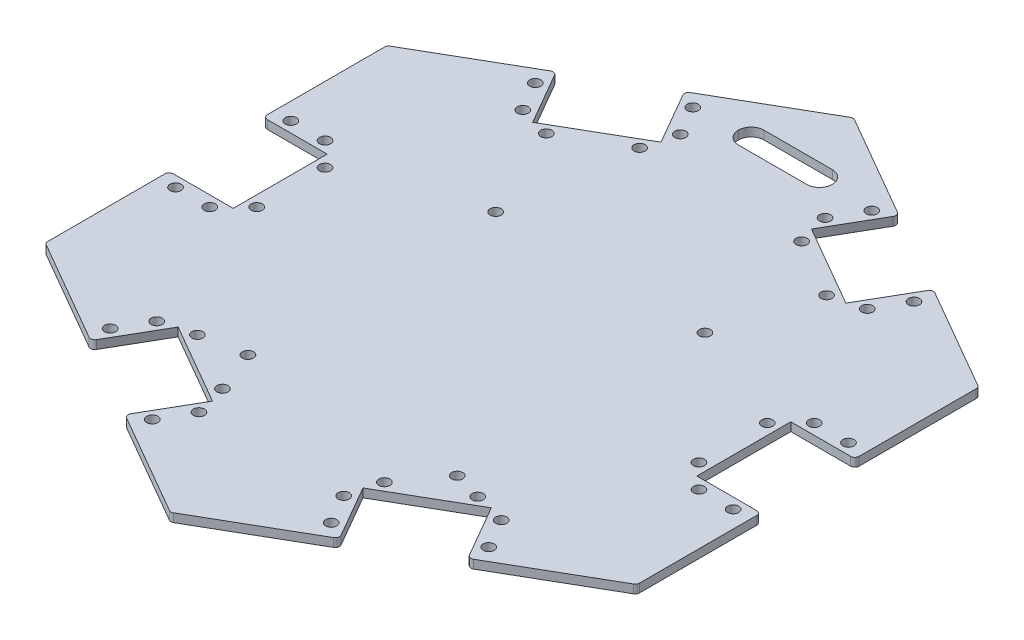
SolidWorks part; units mm, degrees
ref_plane "Front Plane" through (0, 0, 0) normal (0, 0, 1) x (1, 0, 0)
ref_plane "Top Plane" through (0, 0, 0) normal (0, 1, 0) x (1, 0, 0)
ref_plane "Right Plane" through (0, 0, 0) normal (1, 0, 0) x (0, 0, -1)
sketch "Sketch1" plane through (0, 0, 0) normal (0, 1, 0) x (1, 0, 0)
  line L0 (-69.282, 0) -> (69.282, 0) construction
  line L1 (0, -80) -> (69.282, -40)
  line L2 (69.282, -40) -> (69.282, 40)
  line L3 (69.282, 40) -> (0, 80)
  line L4 (0, 80) -> (-69.282, 40)
  line L5 (-69.282, 40) -> (-69.282, -40)
  line L6 (-69.282, -40) -> (0, -80)
  line L7 (-69.282, 40) -> (69.282, -40) construction
  line L8 (0, 80) -> (0, -80) construction
  line L9 (0, 80) -> (69.282, 40)
  line L10 (-69.282, 40) -> (0, 80)
  line L11 (-69.282, -40) -> (-69.282, 40)
  line L12 (0, -80) -> (-69.282, -40)
  line L13 (69.282, -40) -> (0, -80)
  line L14 (69.282, 40) -> (69.282, -40)
  line L15 (-69.282, -40) -> (69.282, 40) construction
  circle A0 centre (0, 0) radius 69.282 construction
  circle A1 centre (65.282, 13.5) radius 1.3
  circle A2 centre (57.282, 13.5) radius 1.3
  circle A3 centre (51.782, 8) radius 1.3
  circle A4 centre (51.782, -8) radius 1.3
  circle A5 centre (57.282, -13.5) radius 1.3
  circle A6 centre (65.282, -13.5) radius 1.3
  circle A7 centre (32.8192, -40.8446) radius 1.3
  circle A8 centre (20.9497, -63.2859) radius 1.3
  circle A9 centre (16.9497, -56.3577) radius 1.3
  circle A10 centre (18.9628, -48.8446) radius 1.3
  circle A11 centre (44.3324, -49.7859) radius 1.3
  circle A12 centre (40.3324, -42.8577) radius 1.3
  circle A13 centre (-44.3324, -49.7859) radius 1.3
  circle A14 centre (-40.3324, -42.8577) radius 1.3
  circle A15 centre (-32.8192, -40.8446) radius 1.3
  circle A16 centre (-18.9628, -48.8446) radius 1.3
  circle A17 centre (-16.9497, -56.3577) radius 1.3
  circle A18 centre (-20.9497, -63.2859) radius 1.3
  circle A19 centre (18.9628, 48.8446) radius 1.3
  circle A20 centre (44.3324, 49.7859) radius 1.3
  circle A21 centre (40.3324, 42.8577) radius 1.3
  circle A22 centre (32.8192, 40.8446) radius 1.3
  circle A23 centre (20.9497, 63.2859) radius 1.3
  circle A24 centre (16.9497, 56.3577) radius 1.3
  circle A25 centre (-65.282, 13.5) radius 1.3
  circle A26 centre (-20.9497, 63.2859) radius 1.3
  circle A27 centre (-16.9497, 56.3577) radius 1.3
  circle A28 centre (-18.9628, 48.8446) radius 1.3
  circle A29 centre (-32.8192, 40.8446) radius 1.3
  circle A30 centre (-44.3324, 49.7859) radius 1.3
  circle A31 centre (-40.3324, 42.8577) radius 1.3
  circle A32 centre (-57.282, 13.5) radius 1.3
  circle A33 centre (-51.782, 8) radius 1.3
  circle A34 centre (-51.782, -8) radius 1.3
  circle A35 centre (-57.282, -13.5) radius 1.3
  circle A36 centre (-65.282, -13.5) radius 1.3
  dimension "D6" = 2.6
  dimension "D1" = 4
  dimension "D2" = 8
  dimension "D3" = 5.5
  dimension "D4" = 5.5
  dimension "D5" = 8
  dimension "D7" = 80
extrude "Boss-Extrude1" add sketch "Sketch1" along normal blind 2 contours L5 L6 L1 L2 L3 L4 A36 A35 A34 A32 A31 A30 A29 A27 A25 A24 A23 A21 A15 A13 A12 A11 A9 A6 A4 A3 A2 A1 region at (0, 0, 0)
sketch "Sketch2" plane through (0, 2, 0) normal (0, 1, 0) x (1, 0, 0)
  line L0 (-69.282, 40) -> (69.282, -40) construction
  line L1 (0, 80) -> (0, -80) construction
  line L2 (-69.282, -40) -> (69.282, 40) construction
  line L3 (69.282, -40) -> (69.282, 40) construction
  line L4 (69.282, 11) -> (54.282, 11)
  line L5 (69.282, 11) -> (69.282, -11)
  line L6 (69.282, -11) -> (54.282, -11)
  line L7 (54.282, 11) -> (54.282, -11)
  line L8 (-69.282, 0) -> (69.282, 0) construction
  line L9 (-69.282, 40) -> (-69.282, -40) construction
  line L10 (44.1673, -54.5) -> (36.6673, -41.5096)
  line L11 (17.6147, -52.5096) -> (36.6673, -41.5096)
  line L12 (25.1147, -65.5) -> (17.6147, -52.5096)
  line L13 (25.1147, -65.5) -> (44.1673, -54.5)
  line L14 (-25.1147, -65.5) -> (-44.1673, -54.5)
  line L15 (-25.1147, -65.5) -> (-17.6147, -52.5096)
  line L16 (-17.6147, -52.5096) -> (-36.6673, -41.5096)
  line L17 (-44.1673, -54.5) -> (-36.6673, -41.5096)
  line L18 (25.1147, 65.5) -> (17.6147, 52.5096)
  line L19 (36.6673, 41.5096) -> (17.6147, 52.5096)
  line L20 (44.1673, 54.5) -> (36.6673, 41.5096)
  line L21 (44.1673, 54.5) -> (25.1147, 65.5)
  line L22 (-44.1673, 54.5) -> (-25.1147, 65.5)
  line L23 (-44.1673, 54.5) -> (-36.6673, 41.5096)
  line L24 (-36.6673, 41.5096) -> (-17.6147, 52.5096)
  line L25 (-25.1147, 65.5) -> (-17.6147, 52.5096)
  line L26 (-69.282, 11) -> (-54.282, 11)
  line L27 (-54.282, 11) -> (-54.282, -11)
  line L28 (-69.282, -11) -> (-54.282, -11)
  line L29 (-69.282, 11) -> (-69.282, -11)
  dimension "D1" = 22
  dimension "D2" = 15
extrude "Cut-Extrude1" cut sketch "Sketch2" against normal up to surface (2 mm away) up to face at (-65.282, 0, 14.8)
fillet "Fillet1" radius 1 18 edges at (-25.1147, 1, -65.5) (-44.1673, 1, -54.5) (-69.282, 1, -40) (-69.282, 1, -11) (-69.282, 1, 11) (-69.282, 1, 40) (-44.1673, 1, 54.5) (-25.1147, 1, 65.5) (0, 1, 80) (25.1147, 1, 65.5) (44.1673, 1, 54.5) (69.282, 1, 40) (69.282, 1, 11) (69.282, 1, -11) (69.282, 1, -40) (44.1673, 1, -54.5) (25.1147, 1, -65.5) (0, 1, -80)
sketch "Sketch3" plane through (0, 2, 0) normal (0, 1, 0) x (1, 0, 0)
  line L0 (0, -79.8453) -> (0, 79.8453) construction
  line L1 (-22.8368, -38.9953) -> (-22.8368, 19.0047) construction
  line L2 (-22.8368, -38.9953) -> (26.1632, -38.9953) construction
  line L3 (26.1632, -38.9953) -> (26.1632, 19.0047) construction
  line L4 (-22.8368, 19.0047) -> (26.1632, 19.0047) construction
  line L7 (-26.3368, -42.4953) -> (-26.3368, 42.5047) construction
  line L8 (-26.3368, -42.4953) -> (29.6632, -42.4953) construction
  line L9 (29.6632, -42.4953) -> (29.6632, 42.5047) construction
  line L10 (-26.3368, 42.5047) -> (29.6632, 42.5047) construction
  circle A0 centre (-22.8368, -38.9953) radius 1.3
  circle A1 centre (-22.8368, 19.0047) radius 1.3
  circle A2 centre (26.1632, 19.0047) radius 1.3
  circle A3 centre (26.1632, -38.9953) radius 1.3
  arc A4 (-0.5, -79.7113) -> (0.5, -79.7113) centre (0, -78.8453) ccw construction
  arc A5 (0.5, 79.7113) -> (-0.5, 79.7113) centre (0, 78.8453) ccw construction
  point P0 (0, 0)
  point P6 (0, 0)
  dimension "D7" = 2.6
  dimension "D8" = 37.35
  dimension "D1" = 85
  dimension "D2" = 56
  dimension "D3" = 49
  dimension "D4" = 58
  dimension "D5" = 3.5
  dimension "D6" = 3.5
extrude "Cut-Extrude2" cut sketch "Sketch3" against normal up to surface (2 mm away) up to face at (0, 0, 0)
sketch "Sketch4" plane through (0, 2, 0) normal (0, 1, 0) x (1, 0, 0)
  line L1 (11, 61) -> (-11, 61)
  line L2 (11, 61) -> (11, 67)
  line L3 (11, 67) -> (-11, 67)
  line L4 (-11, 61) -> (-11, 67)
  line L5 (11, 61) -> (-11, 67) construction
  line L6 (11, 67) -> (-11, 61) construction
  point P0 (0, 64)
  point P5 (0, 0)
  dimension "D1" = 22
  dimension "D2" = 6
  dimension "D3" = 64
extrude "Cut-Extrude3" cut sketch "Sketch4" against normal up to surface (2 mm away) up to face at (26.1632, 0, 40.2953)
fillet "Fillet2" radius 3 4 edges at (11, 1, -67) (-11, 1, -67) (-11, 1, -61) (11, 1, -61)
